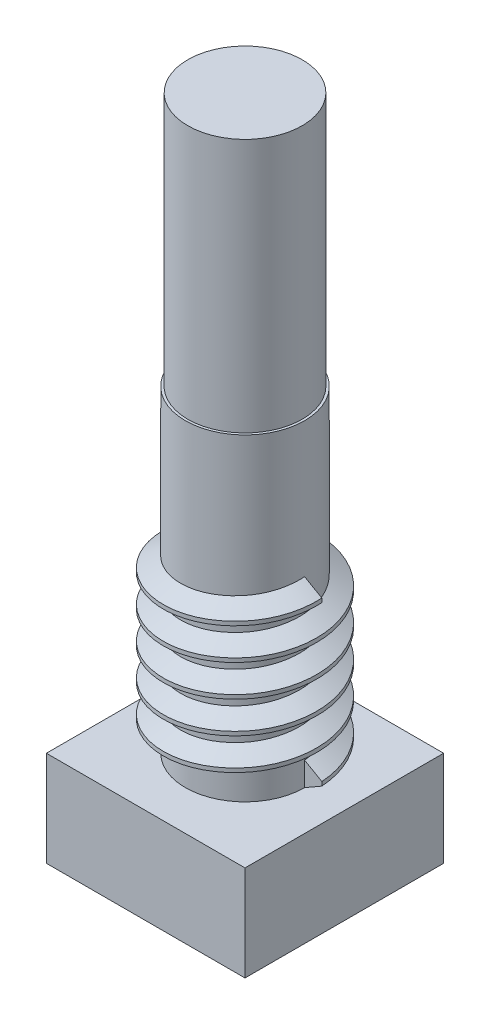
SolidWorks part; units mm, degrees
ref_plane "Front Plane" through (0, 0, 0) normal (0, 0, 1) x (1, 0, 0)
ref_plane "Top Plane" through (0, 0, 0) normal (0, 1, 0) x (1, 0, 0)
ref_plane "Right Plane" through (0, 0, 0) normal (1, 0, 0) x (0, 0, -1)
sketch "Sketch2" plane through (0, 0, 0) normal (0, 1, 0) x (1, 0, 0)
  line L1 (3.9688, -3.9688) -> (-3.9687, -3.9688)
  line L2 (3.9688, -3.9688) -> (3.9688, 3.9687)
  line L3 (3.9688, 3.9687) -> (-3.9687, 3.9687)
  line L4 (-3.9687, -3.9688) -> (-3.9687, 3.9687)
  line L5 (3.9688, -3.9688) -> (-3.9687, 3.9687) construction
  line L6 (3.9688, 3.9687) -> (-3.9687, -3.9688) construction
  dimension "D2" = 7.9375
  dimension "D3" = 7.9375
extrude "Boss-Extrude1" add sketch "Sketch2" along normal blind 3.81
sketch "Sketch3" plane through (0, 3.81, 0) normal (0, 1, 0) x (1, 0, 0)
  circle A0 centre (0, 0) radius 2.3825
  dimension "D1" = 4.765
extrude "Boss-Extrude2" add sketch "Sketch3" along normal blind 25.4
thread "Thread2" pitch 1.27 method extrude profile "Thread Profile2" start angle 0, offset 0, length 6.35, pitch 1.27, diameter 4.765
ref_plane "Plane2" through (2.3825, 3.81, 0) normal (0, 0, 1) x (1, 0, 0)
sketch "Thread Profile2" plane through (2.3825, 3.81, 0) normal (0, 0, 1) x (1, 0, 0)
  line L0 (0, 0) -> (0, 1.27) construction
  line L1 (0, 0) -> (0.6874, 0.3969)
  line L2 (0.6874, 0.3969) -> (0.6874, 0.5556)
  line L3 (0.6874, 0.5556) -> (0, 0.9525)
  line L4 (0.6874, 0.4762) -> (0, 0.4762) construction
  line L11 (0, 0) -> (0, 0.9525)
  point P2 (0, 0)
  dimension "Pitch" = 1.27
  dimension "Profile_Angle" = 60
  dimension "Profile_Land" = 0.1588
  dimension "Profile_Height" = 0.6874
sketch "Sketch4" plane through (0, 29.21, 0) normal (0, 1, 0) x (1, 0, 0)
  circle A0 centre (0, 0) radius 2.286
  dimension "D1" = 4.572
extrude "Cut-Extrude1" cut sketch "Sketch4" against normal blind 12.7 flip side to cut
sketch "Sketch5" plane through (0, 29.21, 0) normal (0, 1, 0) x (1, 0, 0)
  circle A0 centre (0, 0) radius 2.286
extrude "Cut-Extrude2" cut sketch "Sketch5" against normal blind 2.54
